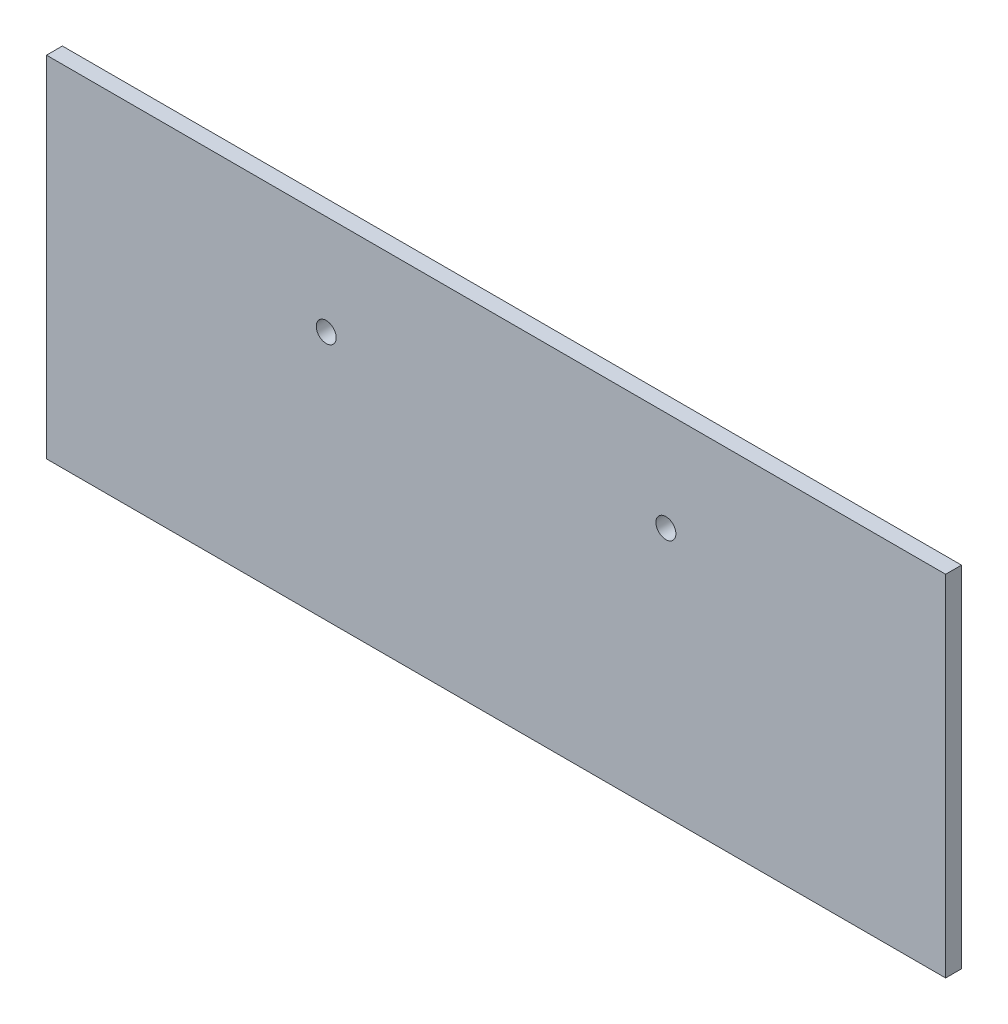
SolidWorks part; units mm, degrees
ref_plane "Front Plane" through (0, 0, 0) normal (0, 0, 1) x (1, 0, 0)
ref_plane "Top Plane" through (0, 0, 0) normal (0, 1, 0) x (1, 0, 0)
ref_plane "Right Plane" through (0, 0, 0) normal (1, 0, 0) x (0, 0, -1)
sketch "Sketch1" plane through (0, 0, 0) normal (0, 0, 1) x (1, 0, 0)
  line L0 (90, 70) -> (90, 0) construction
  line L1 (0, 0) -> (180, 0)
  line L2 (0, 0) -> (0, 70)
  line L3 (0, 70) -> (180, 70)
  line L4 (180, 0) -> (180, 70)
  circle A0 centre (56, 50) radius 2
  circle A1 centre (124, 50) radius 2
  point P11 (0, 0)
  dimension "D3" = 4
  dimension "D1" = 70
  dimension "D2" = 180
  dimension "D4" = 68
  dimension "D5" = 34
  dimension "D6" = 50
extrude "Boss-Extrude1" add sketch "Sketch1" along normal blind 3.175
